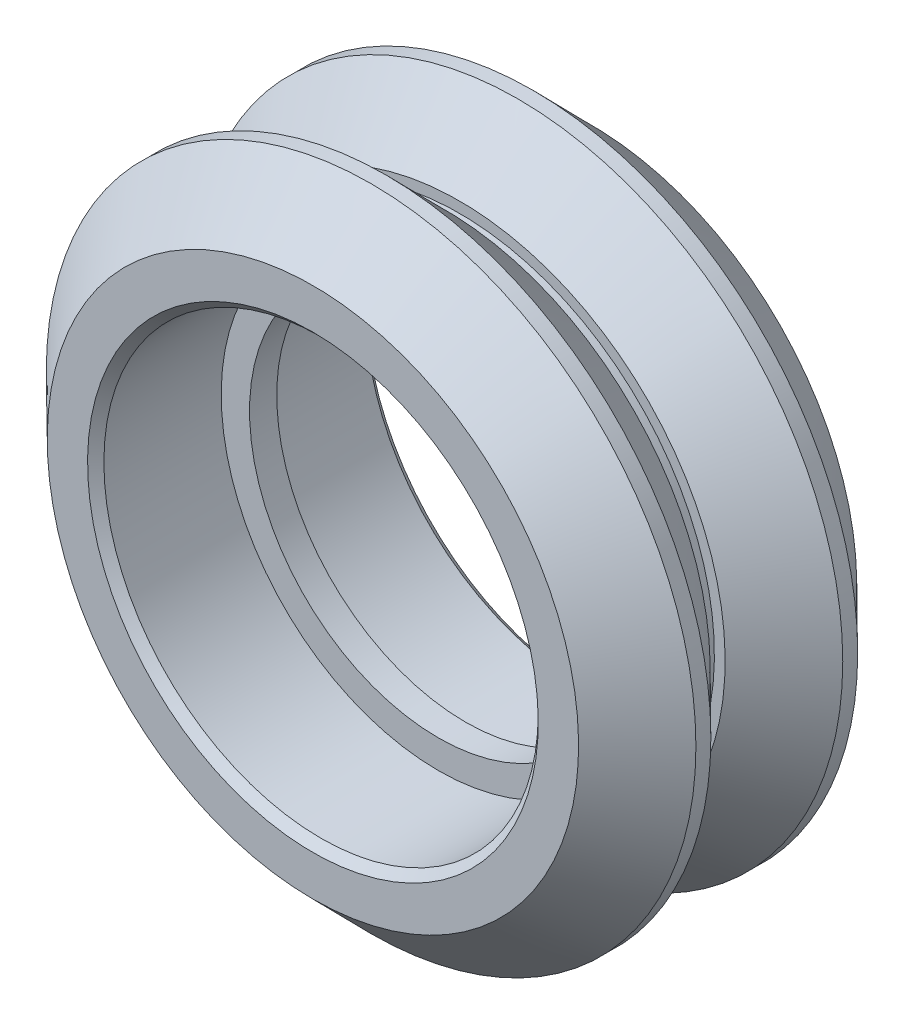
SolidWorks part; units mm, degrees
ref_plane "Front Plane" through (0, 0, 0) normal (0, 0, 1) x (1, 0, 0)
ref_plane "Top Plane" through (0, 0, 0) normal (0, 1, 0) x (1, 0, 0)
ref_plane "Right Plane" through (0, 0, 0) normal (1, 0, 0) x (0, 0, -1)
sketch "Sketch1" plane through (0, 0, 0) normal (1, 0, 0) x (0, 0, -1)
  line L0 (-5.115, 0) -> (5.115, 0) construction
  line L1 (-5.115, 11.945) -> (5.115, 11.945) construction
  line L2 (0, 11.945) -> (0, 0) construction
  line L3 (-5.115, 7.987) -> (5.115, 7.987) construction
  line L4 (-5.115, 9.77) -> (5.115, 9.77) construction
  line L5 (0, 11.945) -> (0, 15.716) construction
  line L6 (-0.5, 6.945) -> (0.5, 6.945) construction
  line L7 (-0.275, 9.375) -> (0.275, 9.375) construction
  line L8 (-2.7, 12.5215) -> (-2.7, 11.945) construction
  line L9 (-2.975, 11.945) -> (-2.425, 11.945)
  line L10 (-2.975, 11.945) -> (-5.115, 9.77)
  line L11 (-5.115, 9.77) -> (-5.115, 7.987)
  line L12 (-5.115, 7.987) -> (-0.5, 7.987)
  line L13 (-0.5, 7.987) -> (-0.5, 6.945)
  line L14 (-0.5, 6.945) -> (0.5, 6.945)
  line L15 (-2.425, 11.945) -> (-0.275, 9.77)
  line L16 (-0.275, 9.77) -> (-0.275, 9.375)
  line L17 (-0.275, 9.375) -> (0.275, 9.375)
  line L18 (2.7, 12.5215) -> (2.7, 11.945) construction
  line L19 (0.275, 9.77) -> (0.275, 9.375)
  line L20 (2.425, 11.945) -> (0.275, 9.77)
  line L21 (0.5, 7.987) -> (0.5, 6.945)
  line L22 (5.115, 7.987) -> (0.5, 7.987)
  line L23 (5.115, 9.77) -> (5.115, 7.987)
  line L24 (2.975, 11.945) -> (5.115, 9.77)
  line L25 (2.975, 11.945) -> (2.425, 11.945)
  point P3 (0, 0)
  point P15 (0, 6.945)
  point P18 (0, 9.375)
  point P23 (-2.7, 11.945)
  point P30 (0, 9.375)
  point P32 (0, 6.945)
  dimension "D1" = 10.23
  dimension "D2" = 11.945
  dimension "D3" = 7.987
  dimension "D4" = 9.77
  dimension "D5" = 6.945
  dimension "D6" = 1
  dimension "D7" = 9.375
  dimension "D8" = 0.55
  dimension "D9" = 2.7
  dimension "D10" = 0.55
ref_axis "Axis1" through (0, 0, 5.115) along (0, 0, -1)
revolve "Revolve1" add sketch "Sketch1" angle 360 about L0
chamfer "Chamfer1" distance 0.3 angle 45 2 edges at (0, -7.987, 5.115) (0, -7.987, -5.115)
